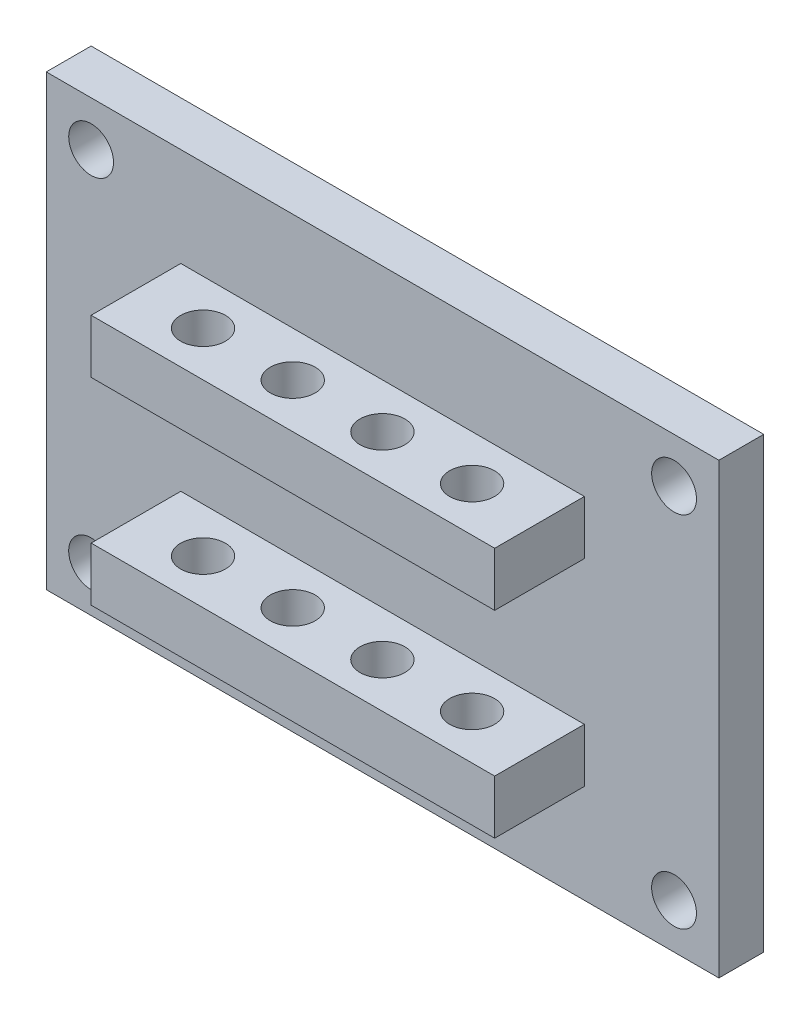
SolidWorks part; units mm, degrees
ref_plane "Plan de face" through (0, 0, 0) normal (0, 0, 1) x (1, 0, 0)
ref_plane "Plan de dessus" through (0, 0, 0) normal (0, 1, 0) x (1, 0, 0)
ref_plane "Plan de droite" through (0, 0, 0) normal (1, 0, 0) x (0, 0, -1)
sketch "Esquisse1" plane through (0, 0, 0) normal (0, 0, 1) x (1, 0, 0)
  line L0 (0, 0) -> (31.3175, 0) construction
  line L1 (-22.5, 14) -> (22.5, 14)
  line L2 (-22.5, 14) -> (-22.5, 8)
  line L3 (-22.5, 8) -> (22.5, 8)
  line L4 (22.5, 14) -> (22.5, 8)
  line L5 (-22.5, 14) -> (22.5, 8) construction
  line L6 (-22.5, 8) -> (22.5, 14) construction
  line L7 (-22.5, -8) -> (22.5, -14) construction
  line L8 (-22.5, -14) -> (22.5, -8) construction
  line L9 (22.5, -14) -> (22.5, -8)
  line L10 (-22.5, -8) -> (22.5, -8)
  line L11 (-22.5, -14) -> (-22.5, -8)
  line L12 (-22.5, -14) -> (22.5, -14)
  point P0 (0, 11)
  point P12 (0, -11)
  dimension "D1" = 45
  dimension "D2" = 6
  dimension "D3" = 11
extrude "Boss.-Extru.1" add sketch "Esquisse1" along normal blind 10
sketch "Esquisse2" plane through (0, 0, 0) normal (0, 0, -1) x (-1, 0, 0)
  line L0 (0, 0) -> (0, 25) construction
  line L1 (-37.5, -25) -> (37.5, -25)
  line L2 (-37.5, -25) -> (-37.5, 25)
  line L3 (-37.5, 25) -> (37.5, 25)
  line L4 (37.5, -25) -> (37.5, 25)
  line L5 (-37.5, -25) -> (37.5, 25) construction
  line L6 (-37.5, 25) -> (37.5, -25) construction
  line L7 (0, 0) -> (37.5, 0) construction
  circle A0 centre (32.5, 20) radius 2.5
  circle A1 centre (-32.5, 20) radius 2.5
  circle A2 centre (-32.5, -20) radius 2.5
  circle A3 centre (32.5, -20) radius 2.5
  point P0 (0, 0)
  dimension "D5" = 5
  dimension "D1" = 50
  dimension "D2" = 75
  dimension "D3" = 5
  dimension "D4" = 5
extrude "Boss.-Extru.2" add sketch "Esquisse2" along normal blind 5
sketch "Esquisse3" plane through (0, -14, 0) normal (0, -1, 0) x (1, 0, 0)
  line L0 (0, 0) -> (0, 10) construction
  line L1 (37.5, 0) -> (-37.5, 0) construction
  line L2 (-22.5, 10) -> (22.5, 10) construction
  line L3 (0, 5) -> (-22.5, 5) construction
  line L4 (-22.5, 10) -> (-22.5, 0) construction
  circle A0 centre (-5, 5.0184) radius 2.5
  circle A1 centre (5, 5.0184) radius 2.5
  circle A2 centre (15, 5.0184) radius 2.5
  circle A3 centre (-15, 5.0184) radius 2.5
  dimension "D2" = 5
  dimension "D1" = 5
  dimension "D3" = 3
  dimension "D4" = 2
extrude "Enlèv. mat.-Extru.1" cut sketch "Esquisse3" against normal up to surface (28 mm away) up to face at (0, 14, 5)
